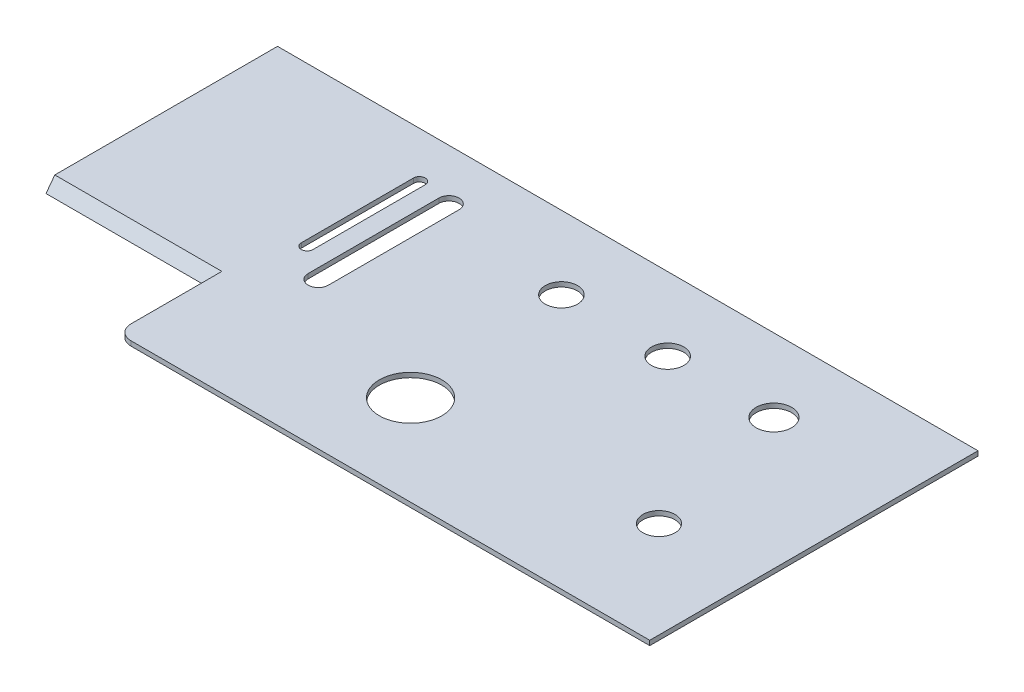
SolidWorks part; units mm, degrees
ref_plane "Front Plane" through (0, 0, 0) normal (0, 0, 1) x (1, 0, 0)
ref_plane "Top Plane" through (0, 0, 0) normal (0, 1, 0) x (1, 0, 0)
ref_plane "Right Plane" through (0, 0, 0) normal (1, 0, 0) x (0, 0, -1)
sketch "Sketch1" plane through (0, 0, 0) normal (0, 1, 0) x (1, 0, 0)
  line L0 (-90.5722, -17.5155) -> (-33.5722, -17.5155) construction
  line L1 (-33.5722, -53.5155) -> (148.4278, -53.5155) construction
  line L2 (-90.5722, -17.5155) -> (-90.5722, 58.4845) construction
  line L3 (-90.5722, 58.4845) -> (148.4278, 58.4845) construction
  line L4 (148.4278, -53.5155) -> (148.4278, 58.4845) construction
  line L5 (-33.5722, -17.5155) -> (-33.5722, -53.5155) construction
  line L6 (-26.4722, 42.7845) -> (-26.4722, 4.4845) construction
  line L7 (-23.4722, 42.7845) -> (-23.4722, 4.4845) construction
  line L8 (-29.4722, 42.7845) -> (-29.4722, 4.4845) construction
  line L9 (-14.7722, 41.1845) -> (-14.7722, -3.4155) construction
  line L10 (-10.1722, 41.1845) -> (-10.1722, -3.4155) construction
  line L11 (-19.3722, 41.1845) -> (-19.3722, -3.4155) construction
  line L12 (-26.4722, 45.7845) -> (-43.4588, 45.7845) construction
  line L13 (-26.4722, 1.4845) -> (-43.4588, 1.4845) construction
  line L14 (-14.7722, -8.0155) -> (-3.3024, -8.0155) construction
  line L15 (-14.7722, 45.7845) -> (0, 45.7845) construction
  line L16 (31.286, 33.4845) -> (122.5273, 33.4845) construction
  arc A0 (-23.4722, 42.7845) -> (-29.4722, 42.7845) centre (-26.4722, 42.7845) ccw construction
  arc A1 (-29.4722, 4.4845) -> (-23.4722, 4.4845) centre (-26.4722, 4.4845) ccw construction
  arc A2 (-10.1722, 41.1845) -> (-19.3722, 41.1845) centre (-14.7722, 41.1845) ccw construction
  arc A3 (-19.3722, -3.4155) -> (-10.1722, -3.4155) centre (-14.7722, -3.4155) ccw construction
  circle A7 centre (35.9778, -22.6655) radius 11.15 construction
  circle A8 centre (115.5278, -17.4655) radius 5.95 construction
  circle A9 centre (31.286, 33.4845) radius 6.25 construction
  circle A10 centre (67.536, 33.4845) radius 6.25 construction
  circle A11 centre (103.786, 33.4845) radius 6.25 construction
  point P0 (0, 0)
  point P10 (-26.4722, 23.6345)
  point P15 (-14.7722, 18.8845)
  dimension "D5" = 3
  dimension "D6" = 4.6
  dimension "D7" = 44.3
  dimension "D9" = 12.5
  dimension "D10" = 22.3
  dimension "D11" = 11.9
  dimension "D14" = 149.1
  dimension "D16" = 12.7
  dimension "D19" = 81.15
  dimension "D1" = 239
  dimension "D2" = 182
  dimension "D3" = 64.1
  dimension "D4" = 75.8
  dimension "D8" = 53.8
  dimension "D12" = 112
  dimension "D13" = 69.55
  dimension "D15" = 12.7
  dimension "D17" = 25
  dimension "D20" = 75.95
  dimension "D21" = 76
  dimension "D22" = 36
  dimension "D18" = 3
sketch "Sketch2" plane through (0, 0, 0) normal (0, 1, 0) x (1, 0, 0)
  line L0 (-90.5722, -17.5155) -> (-33.5722, -17.5155)
  line L1 (-90.5722, 58.4845) -> (148.4278, 58.4845)
  line L2 (-90.5722, 58.4845) -> (-90.5722, -17.5155)
  line L3 (-28.5722, -53.5155) -> (148.4278, -53.5155)
  line L4 (148.4278, 58.4845) -> (148.4278, -53.5155)
  line L5 (-33.5722, -17.5155) -> (-33.5722, -48.5155)
  line L6 (-26.4722, 4.4845) -> (-26.4722, 42.7845) construction
  line L7 (-28.4722, 4.4845) -> (-28.4722, 42.7845)
  line L8 (-24.4722, 4.4845) -> (-24.4722, 42.7845)
  line L9 (-14.7722, 41.1845) -> (-14.7722, -3.4155) construction
  line L10 (-11.3222, 41.1845) -> (-11.3222, -3.4155)
  line L11 (-18.2222, 41.1845) -> (-18.2222, -3.4155)
  arc A0 (-28.4722, 4.4845) -> (-24.4722, 4.4845) centre (-26.4722, 4.4845) ccw
  arc A1 (-24.4722, 42.7845) -> (-28.4722, 42.7845) centre (-26.4722, 42.7845) ccw
  arc A2 (-11.3222, 41.1845) -> (-18.2222, 41.1845) centre (-14.7722, 41.1845) ccw
  arc A3 (-18.2222, -3.4155) -> (-11.3222, -3.4155) centre (-14.7722, -3.4155) ccw
  circle A4 centre (31.286, 33.4845) radius 5.5
  circle A5 centre (67.536, 33.4845) radius 5.5
  circle A6 centre (103.786, 33.4845) radius 6.05
  circle A7 centre (35.9778, -22.6655) radius 10.65
  circle A8 centre (115.5278, -17.4655) radius 5.45
  circle A9 centre (35.9778, -22.6655) radius 11.15 construction
  circle A10 centre (115.5278, -17.4655) radius 5.95 construction
  arc A11 (-33.5722, -48.5155) -> (-28.5722, -53.5155) centre (-28.5722, -48.5155) ccw
  point P15 (-26.4722, 23.6345)
  point P24 (-14.7722, 18.8845)
  point P50 (-33.5722, -53.5155)
  dimension "D1" = 2
  dimension "D2" = 3.45
  dimension "D3" = 11
  dimension "D4" = 11
  dimension "D5" = 12.1
  dimension "D6" = 0.5
  dimension "D7" = 0.5
  dimension "D8" = 5
extrude "Boss-Extrude1" add sketch "Sketch2" along normal blind 1.6
sketch "Sketch3" plane through (-33.5722, 0, 0) normal (-1, 0, 0) x (0, 0, 1)
  line L0 (17.5155, 1.6) -> (20.5155, -2.4)
  line L1 (20.5155, -2.4) -> (17.5155, -2.4)
  line L2 (17.5155, -2.4) -> (17.5155, 1.6)
  dimension "D1" = 3
  dimension "D2" = 4
extrude "Boss-Extrude2" add sketch "Sketch3" along normal blind 57
